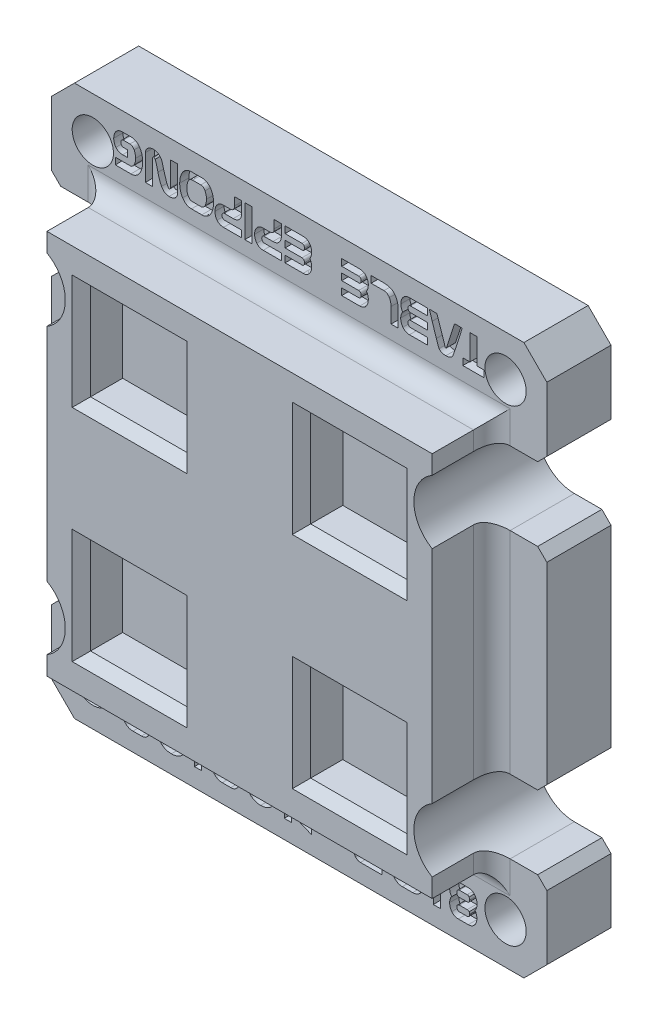
SolidWorks part; units mm, degrees
ref_plane "Plan de face" through (0, 0, 0) normal (0, 0, 1) x (1, 0, 0)
ref_plane "Plan de dessus" through (0, 0, 0) normal (0, 1, 0) x (1, 0, 0)
ref_plane "Plan de droite" through (0, 0, 0) normal (1, 0, 0) x (0, 0, -1)
sketch "Esquisse1" plane through (0, 0, 0) normal (0, 0, 1) x (1, 0, 0)
  line L1 (0, 0) -> (54, 0)
  line L2 (0, 0) -> (0, -60)
  line L3 (0, -60) -> (54, -60)
  line L4 (54, 0) -> (54, -60)
  line L5 (54, -10.5) -> (46, -10.5)
  line L6 (54, 0) -> (54, -60)
  line L7 (54, -10.5) -> (54, -18.5)
  line L8 (54, -18.5) -> (46, -18.5)
  line L9 (46, -10.5) -> (46, -18.5)
  line L10 (0, -10.5) -> (8, -10.5)
  line L11 (0, -10.5) -> (0, -18.5)
  line L12 (0, -18.5) -> (8, -18.5)
  line L13 (8, -10.5) -> (8, -18.5)
  line L14 (54, -41.5) -> (46, -41.5)
  line L15 (54, -41.5) -> (54, -49.5)
  line L16 (54, -49.5) -> (46, -49.5)
  line L17 (46, -41.5) -> (46, -49.5)
  line L18 (0, -41.5) -> (8, -41.5)
  line L19 (0, -41.5) -> (0, -49.5)
  line L20 (0, -49.5) -> (8, -49.5)
  line L21 (8, -41.5) -> (8, -49.5)
  circle A3 centre (4.5, -55.5) radius 2.25
  circle A4 centre (49.5, -55.5) radius 2.25
  circle A5 centre (49.5, -4.5) radius 2.25
  circle A6 centre (4.5, -4.5) radius 2.25
  point P37 (46, -14.5)
  point P38 (8, -14.5)
  point P39 (8, -45.5)
  point P40 (46, -45.5)
  dimension "D14" = 4.5
  dimension "D19" = 4.5
  dimension "D20" = 4.5
  dimension "D21" = 4.5
  dimension "D22" = 4.5
  dimension "D4" = 60
  dimension "D5" = 54
  dimension "D15" = 51
  dimension "D16" = 51
  dimension "D17" = 45
  dimension "D18" = 45
  dimension "D23" = 4.5
  dimension "D24" = 4.5
  dimension "D25" = 4.5
  dimension "D26" = 4.5
  dimension "D27" = 8
  dimension "D28" = 8
  dimension "D29" = 8
  dimension "D30" = 8
  dimension "D31" = 10
  dimension "D32" = 10
  dimension "D33" = 10
  dimension "D34" = 10
  dimension "D35" = 8
  dimension "D36" = 8
  dimension "D37" = 8
  dimension "D38" = 8
extrude "Boss.-Extru.1" add sketch "Esquisse1" along normal blind 7 contours L4 L1 L2 L3 | L4 region at (27, -30, 0)
ref_plane "Plan1" through (0, -30, 0) normal (0, -1, 0) x (-1, 0, 0)
chamfer "Chanfrein1" distance 2.5 angle 45 4 edges at (0, 0, 3.5) (0, -60, 3.5) (54, -60, 3.5) (54, 0, 3.5)
fillet "Congé1" radius 4 8 edges at (46, -10.5, 3.5) (46, -18.5, 3.5) (8, -18.5, 3.5) (8, -10.5, 3.5) (8, -41.5, 3.5) (8, -49.5, 3.5) (46, -41.5, 3.5) (46, -49.5, 3.5)
chamfer "Chanfrein2" distance 1 angle 45 8 edges at (0, -41.5, 3.5) (0, -49.5, 3.5) (0, -18.5, 3.5) (0, -10.5, 3.5) (54, -10.5, 3.5) (54, -18.5, 3.5) (54, -41.5, 3.5) (54, -49.5, 3.5)
sketch "Esquisse3" plane through (0, 0, 7) normal (0, 0, 1) x (1, 0, 0)
  line L0 (2.5, 0) -> (51.5, 0) construction
  line L1 (6, -9) -> (48, -9)
  line L2 (6, -9) -> (6, -51)
  line L3 (6, -51) -> (48, -51)
  line L4 (48, -9) -> (48, -51)
  line L5 (-3.85, -30) -> (3.85, -30) construction
  circle A0 centre (4, -14.5) radius 4
  circle A1 centre (50, -14.5) radius 4
  circle A2 centre (50, -45.5) radius 4
  circle A3 centre (4, -45.5) radius 4
  point P4 (27, -9)
  point P7 (27, 0)
  point P8 (48, -30)
  arc M10 (4, -41.5) -> (8, -45.5) centre (4, -45.5) cw
  arc M11 (8, -45.5) -> (4, -49.5) centre (4, -45.5) cw
  arc M21 (50, -49.5) -> (46, -45.5) centre (50, -45.5) cw
  arc M22 (46, -45.5) -> (50, -41.5) centre (50, -45.5) cw
  arc M28 (50, -18.5) -> (46, -14.5) centre (50, -14.5) cw
  arc M29 (46, -14.5) -> (50, -10.5) centre (50, -14.5) cw
  arc M39 (4, -10.5) -> (8, -14.5) centre (4, -14.5) cw
  arc M40 (8, -14.5) -> (4, -18.5) centre (4, -14.5) cw
  dimension "D3" = 8
  dimension "D4" = 8
  dimension "D5" = 8
  dimension "D6" = 8
  dimension "D1" = 42
  dimension "D2" = 42
extrude "Boss.-Extru.2" add sketch "Esquisse3" along normal blind 6.5 contours L4 L1 L2 L3 M39 M40 M10 M11 M21 M22 M28 M29 region at (27, -30, 7)
sketch "Esquisse4" plane through (0, 0, 13.5) normal (0, 0, 1) x (1, 0, 0)
  line L0 (-3.85, -30) -> (3.85, -30) construction
  line L1 (9.75, -47.25) -> (20.25, -47.25)
  line L2 (9.75, -47.25) -> (9.75, -36.75)
  line L3 (9.75, -36.75) -> (20.25, -36.75)
  line L4 (20.25, -47.25) -> (20.25, -36.75)
  line L5 (6, -51) -> (48, -51) construction
  point P4 (9.75, -42)
  point P7 (15, -36.75)
  point P10 (27, -51)
  dimension "D1" = 10.5
  dimension "D2" = 10.5
  dimension "D3" = 12
  dimension "D4" = 12
extrude "Enlèv. mat.-Extru.1" cut sketch "Esquisse4" against normal blind 4.5 contours L4 L3 L2 L1
ref_plane "Plan2" through (27, 0, 0) normal (-1, 0, 0) x (0, 0, 1)
mirror "Symétrie1" about plane through (0, -30, 0) normal (0, -1, 0) of "Enlèv. mat.-Extru.1"
mirror "Symétrie2" about plane through (27, 0, 0) normal (-1, 0, 0) of "Enlèv. mat.-Extru.1", "Symétrie1"
chamfer "Chanfrein3" distance 1 angle 45 16 edges at (44.25, -42, 13.5) (39, -47.25, 13.5) (33.75, -42, 13.5) (39, -36.75, 13.5) (44.25, -18, 13.5) (39, -12.75, 13.5) (39, -23.25, 13.5) (33.75, -18, 13.5) (20.25, -18, 13.5) (15, -23.25, 13.5) (15, -12.75, 13.5) (9.75, -18, 13.5) (20.25, -42, 13.5) (15, -47.25, 13.5) (15, -36.75, 13.5) (9.75, -42, 13.5)
fillet "Congé2" radius 2 8 edges at (6, -10.0179, 7) (6, -30, 7) (6, -49.9821, 7) (27, -9, 7) (48, -10.0179, 7) (27, -51, 7) (48, -49.9821, 7) (48, -30, 7)
sketch "Esquisse5" plane through (0, 0, 7) normal (0, 0, 1) x (1, 0, 0)
  line L0 (0, -58) -> (54, -58) construction
  line L1 (0, -50.5) -> (0, -57.5) construction
  line L2 (54, -50.5) -> (54, -57.5) construction
  line L3 (2.5, -60) -> (51.5, -60) construction
  line L4 (54, -2) -> (0, -2) construction
  line L5 (54, -2.5) -> (54, -9.5) construction
  line L6 (0, -2.5) -> (0, -9.5) construction
  line L7 (2.5, 0) -> (51.5, 0) construction
  text T0 "guigur 2018" font "Nasalization" height 3.5
  text T1 "TABLE EPIPONG" font "Nasalization" height 3.5
  dimension "D1" = 2
  dimension "D2" = 2
extrude "Enlèv. mat.-Extru.2" cut sketch "Esquisse5" against normal blind 1
equation "\"é\"=1.5583"
equation "\"à\"=2.55842"
